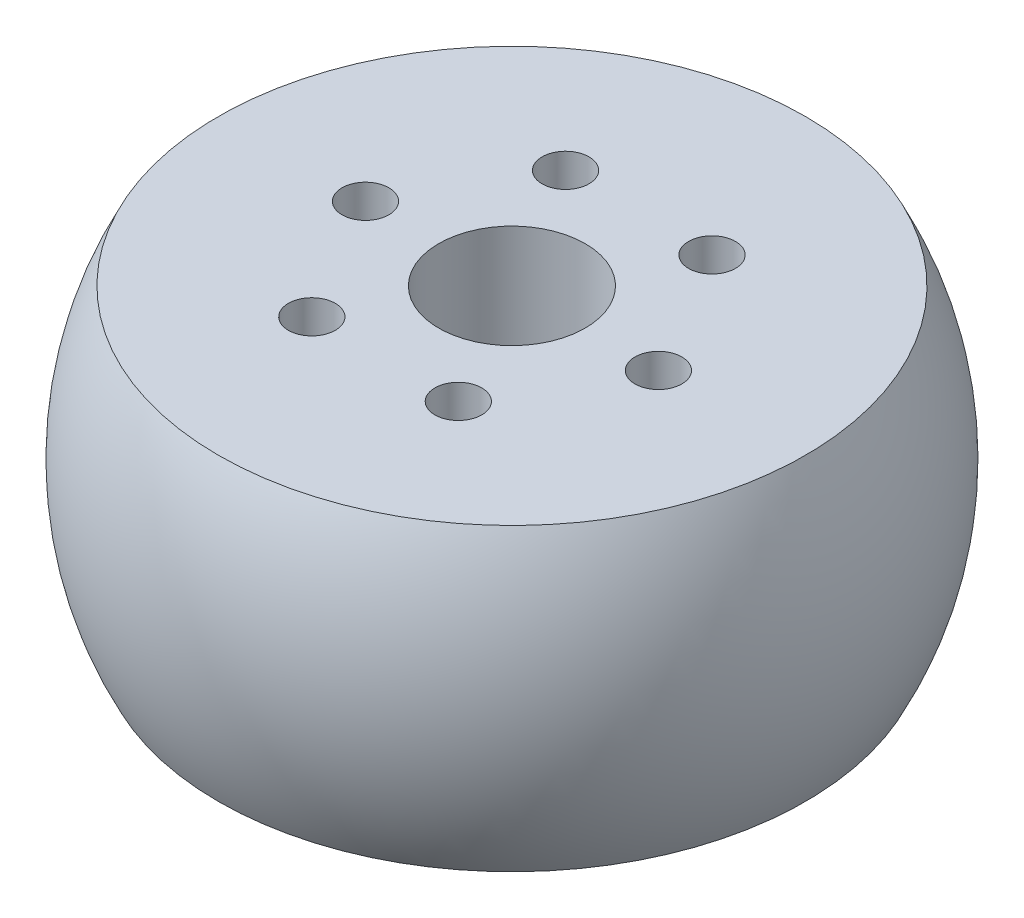
SolidWorks part; units mm, degrees
ref_plane "Front Plane" through (0, 0, 0) normal (0, 0, 1) x (1, 0, 0)
ref_plane "Top Plane" through (0, 0, 0) normal (0, 1, 0) x (1, 0, 0)
ref_plane "Right Plane" through (0, 0, 0) normal (1, 0, 0) x (0, 0, -1)
sketch "Sketch1" plane through (0, 0, 0) normal (1, 0, 0) x (0, 0, -1)
  line L0 (0, -6.5) -> (0, 6.5) construction
  line L1 (3.175, 6.5) -> (12.7233, 6.5)
  line L2 (3.175, 6.5) -> (3.175, -6.5)
  line L3 (3.175, -6.5) -> (12.7233, -6.5)
  line L4 (14.2875, 0) -> (0, 0) construction
  circle A0 centre (0, 0) radius 14.2875 construction
  arc A1 (12.7233, 6.5) -> (12.7233, -6.5) centre (0, 0) cw
  point P4 (0, 0)
  dimension "D1" = 6.35
  dimension "D2" = 13
  dimension "D3" = 14.2875
revolve "Revolve1" add sketch "Sketch1" angle 360 about L0
sketch "Sketch3" plane through (0, 0, 0) normal (0, 1, 0) x (1, 0, 0)
  line L0 (0, 0) -> (6.35, 0) construction
  circle A0 centre (6.35, 0) radius 1.016
  dimension "D1" = 2.032
  dimension "D2" = 6.35
extrude "Cut-Extrude1" cut sketch "Sketch3" against normal through all both and the other way through all
pattern_circular "CirPattern1" count 6 over 360 about axis through (0, -6.5, 0) along (0, -1, 0) of "Cut-Extrude1" reverse direction yes
sketch "Sketch4" plane through (0, 0, 0) normal (0, 1, 0) x (1, 0, 0)
  point P0 (0, 0)
